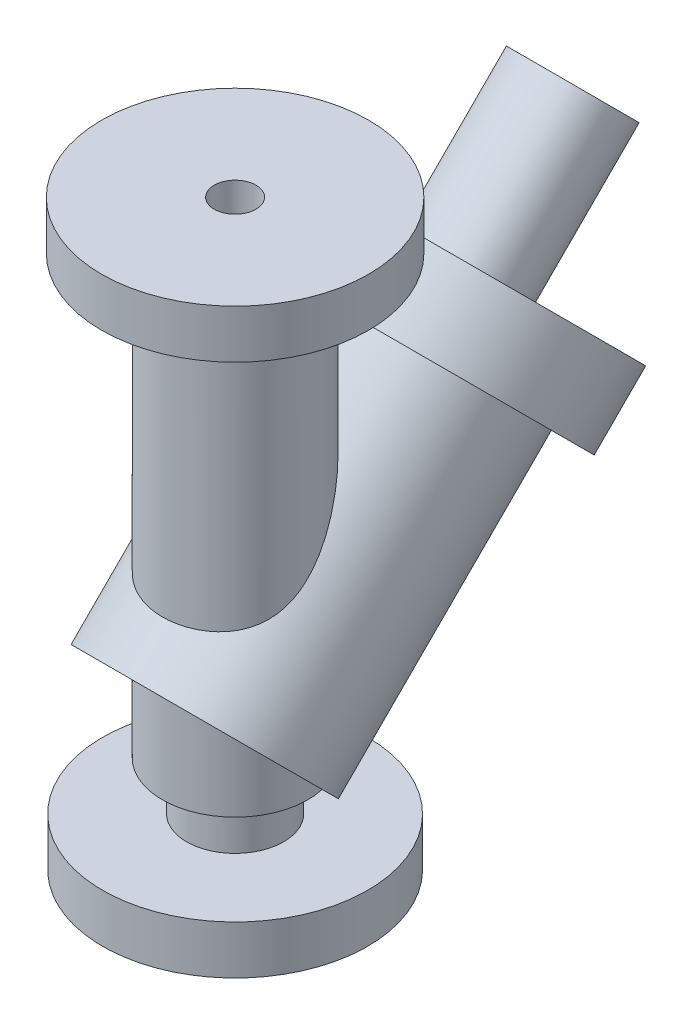
SolidWorks part; units mm, degrees
ref_plane "Front Plane" through (0, 0, 0) normal (0, 0, 1) x (1, 0, 0)
ref_plane "Top Plane" through (0, 0, 0) normal (0, 1, 0) x (1, 0, 0)
ref_plane "Right Plane" through (0, 0, 0) normal (1, 0, 0) x (0, 0, -1)
sketch "Sketch1" plane through (0, 0, 0) normal (0, 1, 0) x (1, 0, 0)
  circle A0 centre (0, 0) radius 12.7
  circle A1 centre (0, 0) radius 5.461
  dimension "D1" = 25.4
  dimension "D2" = 10.922
extrude "Extrude1" add sketch "Sketch1" along normal blind 25.4
sketch "Sketch2" plane through (0, 25.4, 0) normal (0, 1, 0) x (1, 0, 0)
  circle A0 centre (0, 0) radius 5.461
  circle A1 centre (0, 0) radius 19.05
  dimension "D1" = 38.1
extrude "Extrude2" add sketch "Sketch2" along normal blind 127
sketch "Sketch5" plane through (0, 0, 0) normal (0, -1, 0) x (1, 0, 0)
  circle A0 centre (0, 0) radius 12.7
  circle A1 centre (0, 0) radius 34.671
  dimension "D1" = 69.342
extrude "Extrude3" add sketch "Sketch5" against normal blind 12.7
sketch "Sketch6" plane through (0, 0, 0) normal (1, 0, 0) x (0, 0, -1)
  line L0 (0, 0) -> (0, 172.3724)
  line L2 (-34.671, 0) -> (34.671, 0) construction
  line L3 (126.479, 171.9477) -> (0, 45.4687)
  line L4 (87.884, 80.01) -> (61.2126, 106.6814)
  point P3 (87.884, 80.01)
  dimension "D1" = 87.884
  dimension "D2" = 80.01
  dimension "D3" = 37.719
  dimension "D4" = 45
ref_plane "Plane1" through (0, 106.6814, -61.2126) normal (0, -0.7071, 0.7071) x (-1, 0, 0)
sketch "Sketch7" plane through (0, 106.6814, -61.2126) normal (0, -0.7071, 0.7071) x (-1, 0, 0)
  circle A0 centre (0, 0) radius 37.719
extrude "Extrude4" add sketch "Sketch7" along normal blind 19.05
sketch "Sketch9" plane through (0, 83.947, -83.947) normal (0, 0.7071, -0.7071) x (1, 0, 0)
  circle A0 centre (0, -32.1512) radius 28.575
  dimension "D1" = 57.15
extrude "Extrude6" add sketch "Sketch9" against normal blind 97.79
sketch "Sketch10" plane through (0, 83.947, -83.947) normal (0, 0.7071, -0.7071) x (1, 0, 0)
  circle A0 centre (0, -32.1512) radius 14.1871
extrude "Extrude7" add sketch "Sketch10" along normal offset from surface (38.354 mm away) 57.404 up to face at (0, 73.0054, -67.9478)
sketch "Sketch11" plane through (0, 152.4, 0) normal (0, 1, 0) x (1, 0, 0)
  circle A0 centre (0, 0) radius 34.925
  dimension "D1" = 69.85
extrude "Extrude8" add sketch "Sketch11" against normal blind 12.7
sketch "Sketch12" plane through (0, 0, 0) normal (0, -1, 0) x (1, 0, 0)
  circle A0 centre (0, 0) radius 5.461
extrude "Extrude9" cut sketch "Sketch12" against normal through all
